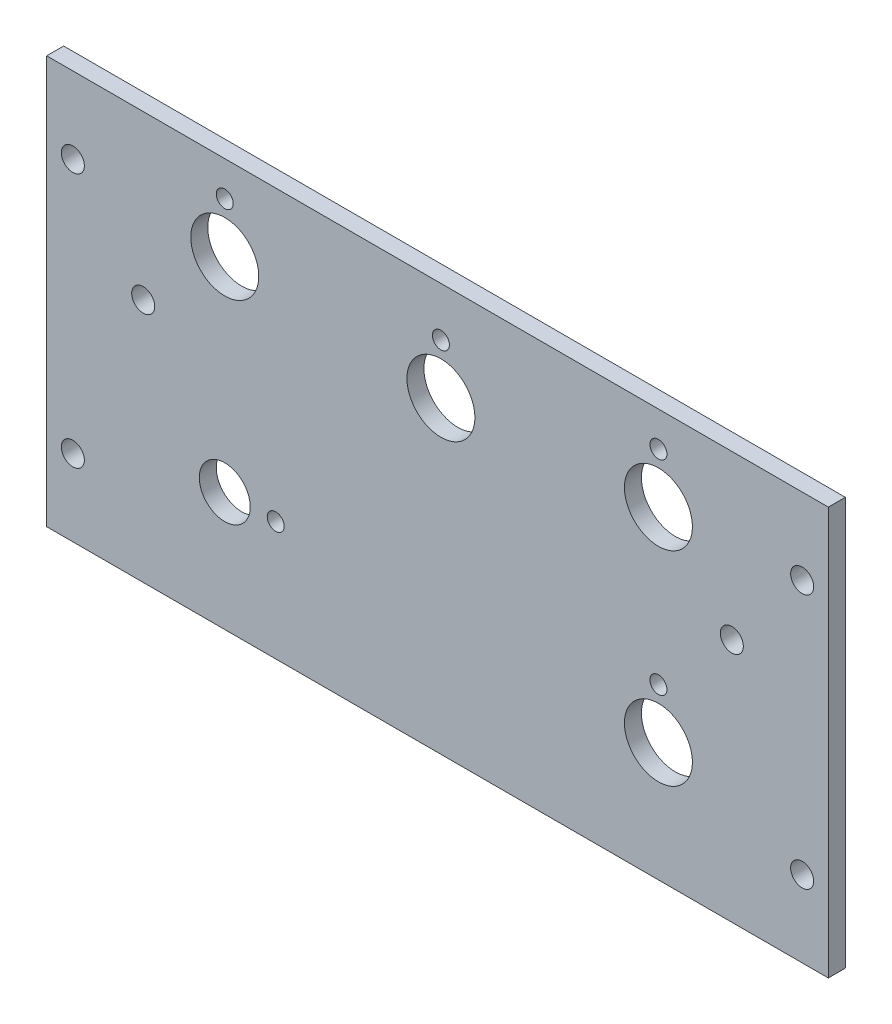
SolidWorks part; units mm, degrees
ref_plane "Front Plane" through (0, 0, 0) normal (0, 0, 1) x (1, 0, 0)
ref_plane "Top Plane" through (0, 0, 0) normal (0, 1, 0) x (1, 0, 0)
ref_plane "Right Plane" through (0, 0, 0) normal (1, 0, 0) x (0, 0, -1)
sketch "Sketch1" plane through (0, 0, 0) normal (0, 0, 1) x (1, 0, 0)
  line L4 (0, 76.2) -> (-146.05, 76.2)
  line L5 (-146.05, 76.2) -> (-146.05, 0)
  line L6 (-146.05, 0) -> (0, 0)
  line L7 (0, 0) -> (0, 76.2)
  line L8 (0, 76.2) -> (-146.05, 76.2)
  line L9 (-146.05, 76.2) -> (-146.05, 0)
  line L10 (-146.05, 0) -> (0, 0)
  line L11 (0, 0) -> (0, 76.2)
  dimension "D1" = 0
extrude "Boss-Extrude1" add sketch "Sketch1" against normal blind 3.175
hole_wizard "#6 Clearance Hole1" positions "Sketch3" profile "Sketch2" hole size "#6" standard "ANSI Inch" end condition through all
sketch "Sketch3" plane through (0, 0, -3.175) normal (0, 0, -1) x (-1, 0, 0)
  point P0 (4.8895, 61.9125)
  point P3 (4.8895, 14.2875)
  point P6 (141.1605, 14.2875)
  point P9 (141.1605, 61.9125)
  point P12 (128.016, 45.72)
  point P15 (18.034, 45.72)
sketch "Sketch2" plane through (-4.8895, 61.9125, -3.175) normal (1, 0, 0) x (0, 1, 0)
  line L0 (0, 0) -> (0, 3.175)
  line L1 (0, 3.175) -> (2.1526, 3.175)
  line L2 (2.1526, 3.175) -> (2.1526, 0)
  line L5 (2.1526, 0) -> (0, 0)
  line L11 (0, -6.35) -> (0, 107.95) construction
  dimension "Thru Hole Dia." = 4.3053
  dimension "Thru Hole Depth" = 3.175
hole_wizard "3/8 (0.375) Diameter Hole1" positions "Sketch7" profile "Sketch6" hole size "3/8" standard "ANSI Inch" end condition through all
sketch "Sketch7" plane through (0, 0, -3.175) normal (0, 0, -1) x (-1, 0, 0)
  line L0 (0, 0) -> (0, 76.2) construction
  line L1 (0, 76.2) -> (146.05, 76.2) construction
  point P3 (112.776, 22.225)
  dimension "D1" = 112.776
  dimension "D2" = 53.975
sketch "Sketch6" plane through (-112.776, 22.225, -3.175) normal (1, 0, 0) x (0, 1, 0)
  line L0 (0, 0) -> (0, 3.175)
  line L1 (0, 3.175) -> (4.7625, 3.175)
  line L2 (4.7625, 3.175) -> (4.7625, 0)
  line L5 (4.7625, 0) -> (0, 0)
  line L11 (0, -6.35) -> (0, 107.95) construction
  dimension "Thru Hole Dia." = 9.525
  dimension "Thru Hole Depth" = 3.175
hole_wizard "1/2 (0.5) Diameter Hole1" positions "Sketch5" profile "Sketch4" hole size "1/2" standard "ANSI Inch" end condition through all
sketch "Sketch5" plane through (0, 0, -3.175) normal (0, 0, -1) x (-1, 0, 0)
  line L0 (0, 0) -> (0, 76.2) construction
  line L1 (0, 76.2) -> (146.05, 76.2) construction
  line L2 (0, 38.1) -> (146.05, 38.1) construction
  line L3 (146.05, 76.2) -> (146.05, 0) construction
  line L5 (112.776, 22.225) -> (31.75, 22.225) construction
  point P0 (31.75, 60.325)
  point P3 (72.39, 57.658)
  point P6 (112.776, 60.325)
  point P29 (31.75, 22.225)
  point P31 (0, 0)
  dimension "D1" = 31.75
  dimension "D2" = 15.875
  dimension "D3" = 2.667
  dimension "D4" = 40.64
  dimension "D5" = 81.026
sketch "Sketch4" plane through (-31.75, 60.325, -3.175) normal (1, 0, 0) x (0, 1, 0)
  line L0 (0, 0) -> (0, 3.175)
  line L1 (0, 3.175) -> (6.35, 3.175)
  line L2 (6.35, 3.175) -> (6.35, 0)
  line L5 (6.35, 0) -> (0, 0)
  line L11 (0, -6.35) -> (0, 107.95) construction
  dimension "Thru Hole Dia." = 12.7
  dimension "Thru Hole Depth" = 3.175
hole_wizard "1/8 (0.125) Diameter Hole1" positions "Sketch9" profile "Sketch8" hole size "1/8" standard "ANSI Inch" end condition through all
sketch "Sketch9" plane through (0, 0, -3.175) normal (0, 0, -1) x (-1, 0, 0)
  line L0 (31.75, 69.6995) -> (31.75, 60.325) construction
  line L2 (72.39, 57.658) -> (72.39, 67.0325) construction
  line L4 (112.776, 60.325) -> (112.776, 69.6995) construction
  line L6 (31.75, 22.225) -> (31.75, 31.5995) construction
  line L8 (72.39, 19.558) -> (72.39, 28.9325) construction
  point P0 (31.75, 69.6995)
  point P2 (112.776, 69.6995)
  point P4 (103.251, 22.225)
  point P14 (72.39, 67.0325)
  point P23 (31.75, 31.5995)
  point P29 (0, 0)
  point P30 (0, 0)
  point P31 (0, 0)
  dimension "D1" = 9.3745
sketch "Sketch8" plane through (-31.75, 69.6995, -3.175) normal (1, 0, 0) x (0, 1, 0)
  line L0 (0, 0) -> (0, 3.175)
  line L1 (0, 3.175) -> (1.5875, 3.175)
  line L2 (1.5875, 3.175) -> (1.5875, 0)
  line L5 (1.5875, 0) -> (0, 0)
  line L11 (0, -6.35) -> (0, 107.95) construction
  dimension "Thru Hole Dia." = 3.175
  dimension "Thru Hole Depth" = 3.175
